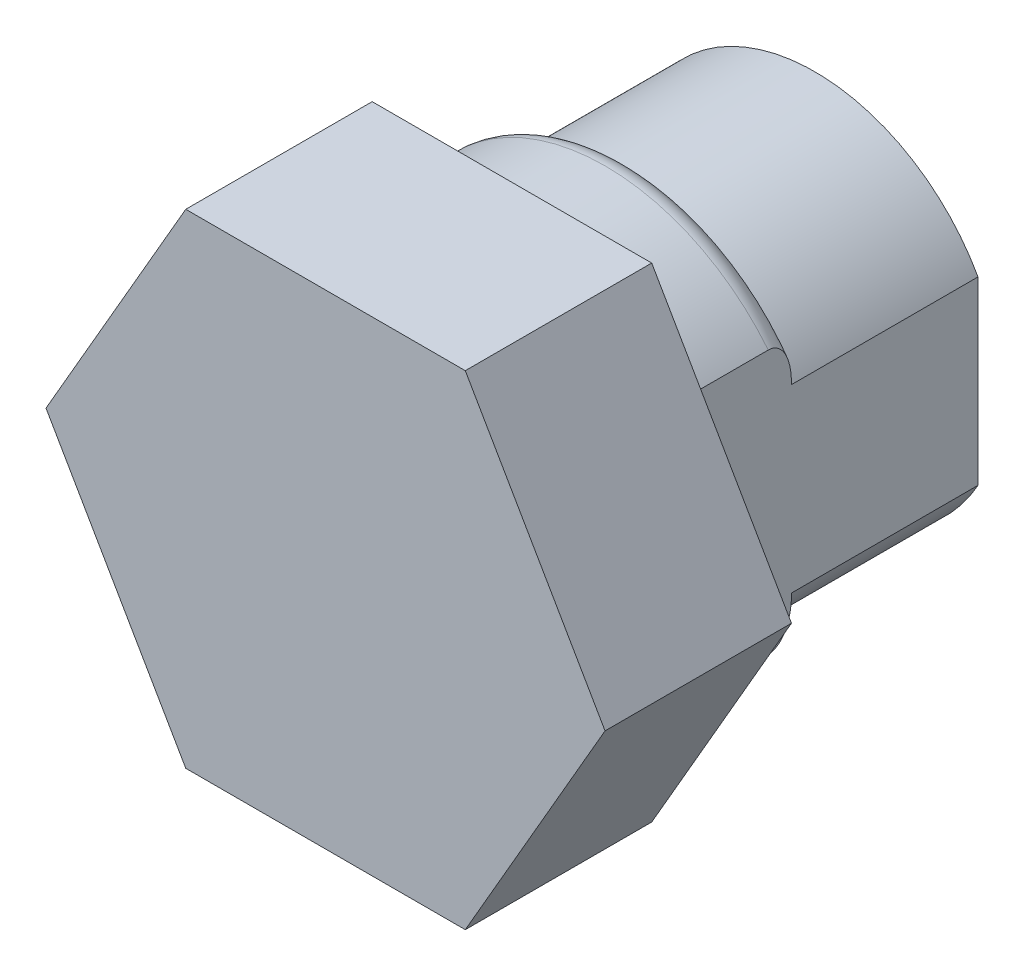
SolidWorks part; units mm, degrees
ref_plane "Ebene vorne" through (0, 0, 0) normal (0, 0, 1) x (1, 0, 0)
ref_plane "Ebene oben" through (0, 0, 0) normal (0, 1, 0) x (1, 0, 0)
ref_plane "Ebene rechts" through (0, 0, 0) normal (1, 0, 0) x (0, 0, -1)
sketch "Skizze1" plane through (0, 0, 0) normal (0, 0, 1) x (1, 0, 0)
  circle A0 centre (0, 0) radius 8
extrude "Aufsatz-Linear austragen1" add sketch "Skizze1" along normal blind 8
sketch "Skizze2" plane through (0, 0, 8) normal (0, 0, 1) x (1, 0, 0)
  circle A0 centre (0, 0) radius 9
extrude "Aufsatz-Linear austragen2" add sketch "Skizze2" along normal blind 5
sketch "Skizze3" plane through (0, 0, 13) normal (0, 0, 1) x (1, 0, 0)
  line L1 (11.9953, 0) -> (5.9976, 10.3882)
  line L2 (5.9976, 10.3882) -> (-5.9976, 10.3882)
  line L3 (-5.9976, 10.3882) -> (-11.9953, 0)
  line L4 (-11.9953, 0) -> (-5.9976, -10.3882)
  line L5 (-5.9976, -10.3882) -> (5.9976, -10.3882)
  line L6 (5.9976, -10.3882) -> (11.9953, 0)
  circle A0 centre (0, 0) radius 10.3882 construction
extrude "Aufsatz-Linear austragen3" add sketch "Skizze3" along normal blind 8
sketch "Skizze4" plane through (0, 0, 0) normal (0, 0, -1) x (-1, 0, 0)
  line L0 (0, 0) -> (0, 3.5253)
  line L1 (-10, -9.5687) -> (-7, -9.5687)
  line L2 (-10, -9.5687) -> (-10, 9.4811)
  line L3 (-10, 9.4811) -> (-7, 9.4811)
  line L4 (-7, -9.5687) -> (-7, 9.4811)
  line L5 (10, 9.4811) -> (7, 9.4811)
  line L6 (7, -9.5687) -> (7, 9.4811)
  line L7 (10, -9.5687) -> (7, -9.5687)
  line L8 (10, -9.5687) -> (10, 9.4811)
  circle M10 centre (0, 0) radius 8
  dimension "D1" = 3
  dimension "D2" = 10
extrude "Schnitt-Linear austragen1" cut sketch "Skizze4" against normal blind 13 contours L1 L4 L3 L2 M10 | L4 M10 | L6 M10 | L7 L8 L5 L6 M10 region at (8.6106, -0.0482, 0) region at (7.4022, 0, 0) region at (-8.6106, -0.0482, 0) region at (-7.4022, 0, 0)
fillet "Verrundung1" radius 1 2 edges at (0, -9, 8) (0, 9, 8)
sketch "Skizze5" plane through (0, 0, 13) normal (0, 0, -1) x (-1, 0, 0)
  line L0 (5.9976, -10.3882) -> (-5.9976, -10.3882) construction
  line L1 (-0.5, -7.0725) -> (0.5, -7.0725)
  line L2 (-0.5, -7.0725) -> (-0.5, -10.3882)
  line L3 (-0.5, -10.3882) -> (0.5, -10.3882)
  line L4 (0.5, -7.0725) -> (0.5, -10.3882)
  dimension "D1" = 1
  dimension "D2" = 0.5
extrude "Aufsatz-Linear austragen4" add sketch "Skizze5" along normal blind 13
